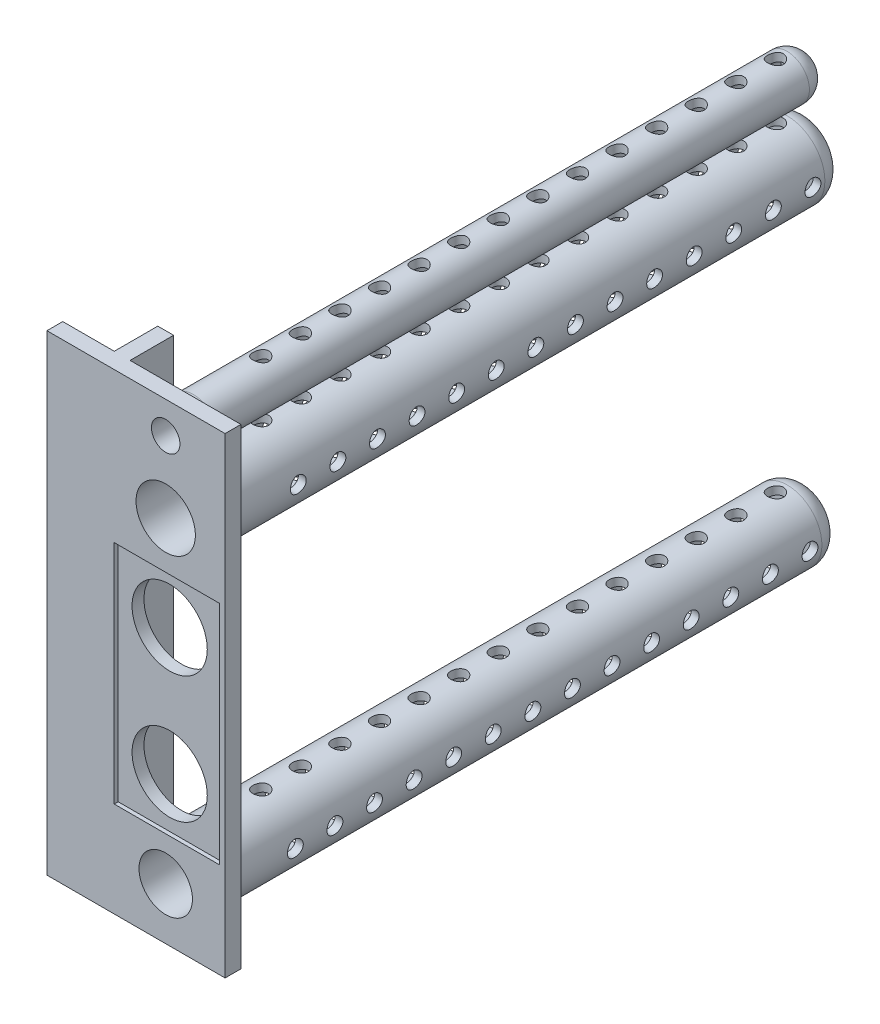
SolidWorks part; units mm, degrees
ref_plane "Piano frontale" through (0, 0, 0) normal (0, 0, 1) x (1, 0, 0)
ref_plane "Piano superiore" through (0, 0, 0) normal (0, 1, 0) x (1, 0, 0)
ref_plane "Piano destro" through (0, 0, 0) normal (1, 0, 0) x (0, 0, -1)
sketch "Schizzo1" plane through (0, 0, 0) normal (0, 0, 1) x (1, 0, 0)
  line L1 (-30, 59.55) -> (30, 59.55)
  line L2 (-30, 59.55) -> (-30, -59.55)
  line L3 (-30, -59.55) -> (30, -59.55)
  line L4 (30, 59.55) -> (30, -59.55)
  line L5 (-30, 59.55) -> (30, -59.55) construction
  line L6 (-30, -59.55) -> (30, 59.55) construction
  point P0 (0, 0)
  dimension "D1" = 119.1
  dimension "D2" = 60
extrude "Estrusione-Estrusione1" add sketch "Schizzo1" along normal blind 4
sketch "Schizzo3" plane through (0, 0, 0) normal (0, 0, 1) x (1, 0, 0)
  line L5 (13.0054, -35.9995) -> (13.0054, 9.0005)
  line L6 (13.0054, -35.9995) -> (33.0054, -35.9995)
  line L7 (33.0054, -35.9995) -> (33.0054, 9.0005)
  line L8 (13.0054, 9.0005) -> (33.0054, 9.0005)
  circle A3 centre (0, -22.9025) radius 9.5
  circle A4 centre (0, 9.0975) radius 9.5
  point P8 (30.6054, -13.3495)
  dimension "D1" = 19
  dimension "D2" = 19
  dimension "D3" = 32
extrude "Taglio-Estrusione1" cut sketch "Schizzo3" along normal blind 4 contours A4 | A3
sketch "Schizzo4" plane through (0, 0, 4) normal (0, 0, 1) x (1, 0, 0)
  line L0 (0, -0.4025) -> (0, -13.4025) construction
  line L2 (-13.6, 21.6975) -> (13.6, 21.6975)
  line L3 (-13.6, 21.6975) -> (-13.6, -35.5025)
  line L4 (-13.6, -35.5025) -> (13.6, -35.5025)
  line L5 (13.6, 21.6975) -> (13.6, -35.5025)
  line L6 (-13.6, 21.6975) -> (13.6, -35.5025) construction
  line L7 (-13.6, -35.5025) -> (13.6, 21.6975) construction
  circle A0 centre (0, 9.0975) radius 9.5 construction
  circle A1 centre (0, -22.9025) radius 9.5 construction
  point P7 (0, -6.9025)
  dimension "D1" = 57.2
  dimension "D2" = 27.2
extrude "Taglio-Estrusione2" cut sketch "Schizzo4" against normal blind 1
ref_plane "Piano1" through (0, -35.5025, 0) normal (0, 1, 0) x (1, 0, 0)
sketch "Schizzo6" plane through (0, 0, 4) normal (0, 0, 1) x (1, 0, 0)
  line L0 (30, 59.55) -> (-30, 59.55) construction
  circle A0 centre (0, 51.55) radius 3.6
  circle A1 centre (0, 33.55) radius 7.5
  circle A2 centre (0, -46.45) radius 6.75
  dimension "D1" = 8
  dimension "D4" = 7.2
  dimension "D5" = 15
  dimension "D2" = 18
  dimension "D3" = 80
extrude "Taglio-Estrusione3" cut sketch "Schizzo6" against normal blind 31
sketch "Schizzo7" plane through (0, 0, 4) normal (0, 0, 1) x (1, 0, 0)
  line L0 (30, 59.55) -> (-30, 59.55) construction
  line L1 (-13, 59.55) -> (-17, 59.55)
  line L2 (-13, 59.55) -> (-13, -59.55)
  line L3 (-13, -59.55) -> (-17, -59.55)
  line L4 (-17, 59.55) -> (-17, -59.55)
  line L5 (-30, -59.55) -> (30, -59.55) construction
  line L7 (-30, 59.55) -> (-30, -59.55) construction
  dimension "D1" = 13
  dimension "D2" = 4
extrude "Estrusione-Estrusione2" add sketch "Schizzo7" against normal blind 15
sketch "Schizzo8" plane through (0, 0, 4) normal (0, 0, 1) x (1, 0, 0)
  line L0 (-30, -59.55) -> (30, -59.55) construction
  line L1 (30, 59.55) -> (15, 59.55)
  line L2 (30, 59.55) -> (30, -59.55)
  line L3 (30, -59.55) -> (15, -59.55)
  line L4 (15, 59.55) -> (15, -59.55)
  dimension "D1" = 15
extrude "Taglio-Estrusione4" cut sketch "Schizzo8" against normal blind 4
sketch "Schizzo9" plane through (0, 0, 0) normal (0, 0, -1) x (-1, 0, 0)
  circle A0 centre (0, 51.55) radius 3.6
  circle A1 centre (0, 51.55) radius 5.6
  circle A2 centre (0, 33.55) radius 7.5
  circle A3 centre (0, 33.55) radius 9.5
  circle A4 centre (0, -46.45) radius 6.75
  circle A5 centre (0, -46.45) radius 8.75
  dimension "D1" = 2
  dimension "D2" = 2
  dimension "D3" = 2
extrude "Estrusione-Estrusione3" add sketch "Schizzo9" along normal blind 155
sketch "Schizzo10" plane through (0, 0, -155) normal (0, 0, -1) x (-1, 0, 0)
  circle A0 centre (0, 51.55) radius 5.6
  circle A1 centre (0, 33.55) radius 9.5
  circle A2 centre (0, -46.45) radius 8.75
extrude "Estrusione-Estrusione4" add sketch "Schizzo10" along normal blind 3
fillet "Raccordo1" radius 5 3 edges at (-8.75, -46.45, -158) (-9.5, 33.55, -158) (-5.6, 51.55, -158)
fillet "Raccordo2" radius 3 3 edges at (5.6, 51.55, 0) (9.5, 33.55, 0) (8.75, -46.45, 0)
sketch "Schizzo11" plane through (0, 0, 0) normal (0, 1, 0) x (1, 0, 0)
  line L0 (-5.6, 153) -> (5.6, 153) construction
  circle A0 centre (0, 150) radius 2
  circle A1 centre (0, 140) radius 2
  circle A2 centre (0, 130) radius 2
  circle A3 centre (0, 120) radius 2
  circle A4 centre (0, 110) radius 2
  circle A5 centre (0, 100) radius 2
  circle A6 centre (0, 90) radius 2
  circle A7 centre (0, 80) radius 2
  circle A8 centre (0, 70) radius 2
  circle A9 centre (0, 60) radius 2
  circle A10 centre (0, 50) radius 2
  circle A11 centre (0, 40) radius 2
  circle A12 centre (0, 30) radius 2
  circle A13 centre (0, 20) radius 2
  dimension "D1" = 4
  dimension "D2" = 3
  dimension "D3" = 14
extrude "Taglio-Estrusione5" cut sketch "Schizzo11" against normal mid plane 221
sketch "Schizzo12" plane through (0, 0, 0) normal (1, 0, 0) x (0, 0, -1)
  line L0 (153, -55.2) -> (153, -37.7) construction
  circle A0 centre (150, -46.45) radius 2
  circle A1 centre (140, -46.45) radius 2
  circle A2 centre (130, -46.45) radius 2
  circle A3 centre (120, -46.45) radius 2
  circle A4 centre (110, -46.45) radius 2
  circle A5 centre (100, -46.45) radius 2
  circle A6 centre (90, -46.45) radius 2
  circle A7 centre (80, -46.45) radius 2
  circle A8 centre (70, -46.45) radius 2
  circle A9 centre (60, -46.45) radius 2
  circle A10 centre (50, -46.45) radius 2
  circle A11 centre (40, -46.45) radius 2
  circle A12 centre (30, -46.45) radius 2
  circle A13 centre (20, -46.45) radius 2
  circle A105 centre (140, 33.55) radius 2
  circle A106 centre (130, 33.55) radius 2
  circle A107 centre (120, 33.55) radius 2
  circle A108 centre (110, 33.55) radius 2
  circle A109 centre (100, 33.55) radius 2
  circle A110 centre (90, 33.55) radius 2
  circle A111 centre (80, 33.55) radius 2
  circle A112 centre (70, 33.55) radius 2
  circle A113 centre (60, 33.55) radius 2
  circle A114 centre (50, 33.55) radius 2
  circle A115 centre (40, 33.55) radius 2
  circle A116 centre (30, 33.55) radius 2
  circle A117 centre (20, 33.55) radius 2
  circle A125 centre (150, 33.55) radius 2
  circle A126 centre (20, 23.55) radius 2 [skipped]
  circle A127 centre (30, 23.55) radius 2 [skipped]
  circle A128 centre (40, 23.55) radius 2 [skipped]
  circle A129 centre (50, 23.55) radius 2 [skipped]
  circle A130 centre (60, 23.55) radius 2 [skipped]
  circle A131 centre (70, 23.55) radius 2 [skipped]
  circle A132 centre (80, 23.55) radius 2 [skipped]
  circle A133 centre (90, 23.55) radius 2 [skipped]
  circle A134 centre (100, 23.55) radius 2 [skipped]
  circle A135 centre (110, 23.55) radius 2 [skipped]
  circle A136 centre (120, 23.55) radius 2 [skipped]
  circle A137 centre (130, 23.55) radius 2 [skipped]
  circle A138 centre (140, 23.55) radius 2 [skipped]
  circle A139 centre (150, 23.55) radius 2 [skipped]
  circle A140 centre (140, 13.55) radius 2 [skipped]
  circle A141 centre (130, 13.55) radius 2 [skipped]
  circle A142 centre (120, 13.55) radius 2 [skipped]
  circle A143 centre (110, 13.55) radius 2 [skipped]
  circle A144 centre (100, 13.55) radius 2 [skipped]
  circle A145 centre (90, 13.55) radius 2 [skipped]
  circle A146 centre (80, 13.55) radius 2 [skipped]
  circle A147 centre (70, 13.55) radius 2 [skipped]
  circle A148 centre (60, 13.55) radius 2 [skipped]
  circle A149 centre (50, 13.55) radius 2 [skipped]
  circle A150 centre (40, 13.55) radius 2 [skipped]
  circle A151 centre (30, 13.55) radius 2 [skipped]
  circle A152 centre (20, 13.55) radius 2 [skipped]
  circle A153 centre (20, 3.55) radius 2 [skipped]
  circle A154 centre (20, -6.45) radius 2 [skipped]
  circle A155 centre (20, -16.45) radius 2 [skipped]
  circle A156 centre (20, -26.45) radius 2 [skipped]
  circle A157 centre (20, -36.45) radius 2 [skipped]
  circle A158 centre (30, -36.45) radius 2 [skipped]
  circle A159 centre (40, -36.45) radius 2 [skipped]
  circle A160 centre (50, -36.45) radius 2 [skipped]
  circle A161 centre (60, -36.45) radius 2 [skipped]
  circle A162 centre (70, -36.45) radius 2 [skipped]
  circle A163 centre (80, -36.45) radius 2 [skipped]
  circle A164 centre (90, -36.45) radius 2 [skipped]
  circle A165 centre (100, -36.45) radius 2 [skipped]
  circle A166 centre (110, -36.45) radius 2 [skipped]
  circle A167 centre (120, -36.45) radius 2 [skipped]
  circle A168 centre (130, -36.45) radius 2 [skipped]
  circle A169 centre (140, -36.45) radius 2 [skipped]
  circle A170 centre (150, -36.45) radius 2 [skipped]
  circle A171 centre (150, -26.45) radius 2 [skipped]
  circle A172 centre (150, -16.45) radius 2 [skipped]
  circle A173 centre (150, -6.45) radius 2 [skipped]
  circle A174 centre (150, 3.55) radius 2 [skipped]
  circle A175 centre (150, 13.55) radius 2 [skipped]
  circle A176 centre (140, 3.55) radius 2 [skipped]
  circle A177 centre (130, 3.55) radius 2 [skipped]
  circle A178 centre (120, 3.55) radius 2 [skipped]
  circle A179 centre (110, 3.55) radius 2 [skipped]
  circle A180 centre (80, 3.55) radius 2 [skipped]
  circle A181 centre (70, 3.55) radius 2 [skipped]
  circle A182 centre (60, 3.55) radius 2 [skipped]
  circle A183 centre (50, 3.55) radius 2 [skipped]
  circle A184 centre (40, 3.55) radius 2 [skipped]
  circle A185 centre (30, 3.55) radius 2 [skipped]
  circle A186 centre (30, -6.45) radius 2 [skipped]
  circle A187 centre (40, -6.45) radius 2 [skipped]
  circle A188 centre (50, -6.45) radius 2 [skipped]
  circle A189 centre (60, -6.45) radius 2 [skipped]
  circle A190 centre (70, -6.45) radius 2 [skipped]
  circle A191 centre (80, -6.45) radius 2 [skipped]
  circle A192 centre (90, -6.45) radius 2 [skipped]
  circle A193 centre (100, -6.45) radius 2 [skipped]
  circle A194 centre (110, -6.45) radius 2 [skipped]
  circle A195 centre (120, -6.45) radius 2 [skipped]
  circle A196 centre (130, -6.45) radius 2 [skipped]
  circle A197 centre (140, -6.45) radius 2 [skipped]
  circle A198 centre (100, 3.55) radius 2 [skipped]
  circle A199 centre (90, 3.55) radius 2 [skipped]
  circle A200 centre (30, -16.45) radius 2 [skipped]
  circle A201 centre (30, -26.45) radius 2 [skipped]
  circle A202 centre (40, -26.45) radius 2 [skipped]
  circle A203 centre (40, -16.45) radius 2 [skipped]
  circle A204 centre (60, -26.45) radius 2 [skipped]
  circle A205 centre (50, -26.45) radius 2 [skipped]
  circle A206 centre (50, -16.45) radius 2 [skipped]
  circle A207 centre (60, -16.45) radius 2 [skipped]
  circle A208 centre (70, -16.45) radius 2 [skipped]
  circle A209 centre (70, -26.45) radius 2 [skipped]
  circle A210 centre (80, -26.45) radius 2 [skipped]
  circle A211 centre (80, -16.45) radius 2 [skipped]
  circle A212 centre (90, -16.45) radius 2 [skipped]
  circle A213 centre (90, -26.45) radius 2 [skipped]
  circle A214 centre (100, -16.45) radius 2 [skipped]
  circle A215 centre (100, -26.45) radius 2 [skipped]
  circle A216 centre (110, -16.45) radius 2 [skipped]
  circle A217 centre (110, -26.45) radius 2 [skipped]
  circle A218 centre (120, -16.45) radius 2 [skipped]
  circle A219 centre (120, -26.45) radius 2 [skipped]
  circle A220 centre (130, -16.45) radius 2 [skipped]
  circle A221 centre (130, -26.45) radius 2 [skipped]
  circle A222 centre (140, -26.45) radius 2 [skipped]
  circle A223 centre (140, -16.45) radius 2 [skipped]
  dimension "D1" = 4
  dimension "D2" = 3
  dimension "D3" = 14
  dimension "D4" = 9
extrude "Taglio-Estrusione6" cut sketch "Schizzo12" against normal mid plane 221
